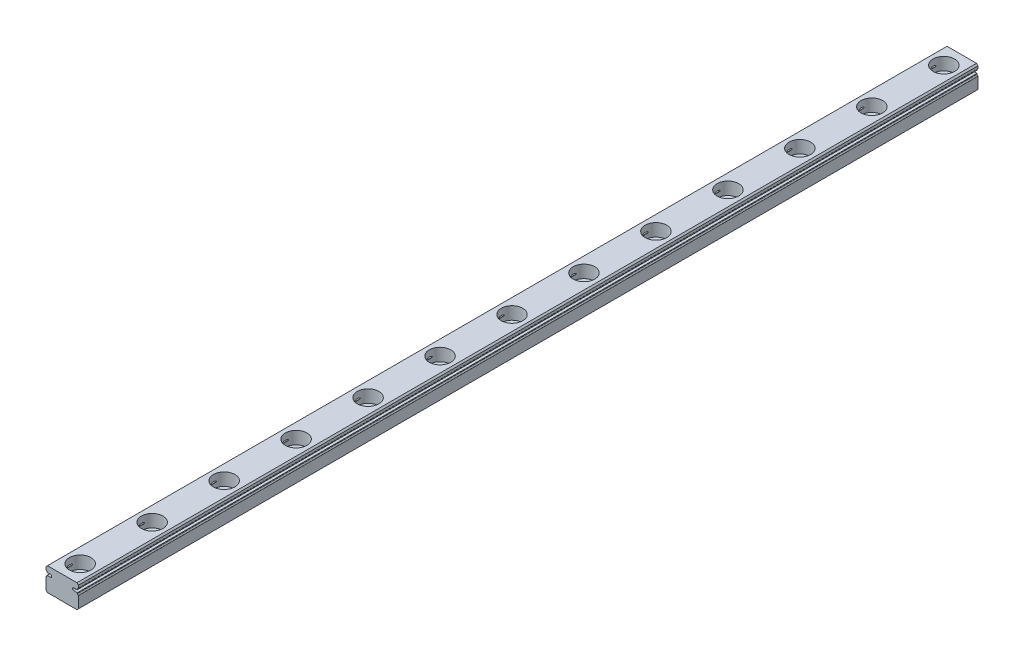
SolidWorks part; units mm, degrees
ref_plane "Alzado" through (0, 0, 0) normal (0, 0, 1) x (1, 0, 0)
ref_plane "Planta" through (0, 0, 0) normal (0, 1, 0) x (1, 0, 0)
ref_plane "Vista lateral" through (0, 0, 0) normal (1, 0, 0) x (0, 0, -1)
ref_plane "Plano1" through (0, 3.3057, 0) normal (0, 1, 0) x (1, 0, 0)
sketch "Croquis1" plane through (0, 3.3057, 0) normal (0, 1, 0) x (1, 0, 0)
  line L0 (4.5, 0) -> (-4.5, 0)
  line L1 (-4.5, 0) -> (-4.5, -250)
  line L2 (-4.5, -250) -> (4.5, -250)
  line L3 (4.5, -250) -> (4.5, 0)
  dimension "D1" = 9
  dimension "D2" = 250
extrude "Saliente-Extruir1" add sketch "Croquis1" against normal blind 6.5
sketch "Croquis2" plane through (0, 0, 0) normal (0, 0, -1) x (-1, 0, 0)
  line L0 (1.6, -3.1943) -> (2.1, -3.1943)
  arc A0 (2.1, -3.1943) -> (1.6, -3.1943) centre (1.85, -3.4568) ccw
extrude "Cortar-Extruir1" cut sketch "Croquis2" against normal through all
sketch "Croquis3" plane through (0, 0, 0) normal (0, 0, -1) x (-1, 0, 0)
  line L0 (-4.5, 1.6457) -> (-4.5, 0.9457)
  line L1 (-4.5, 0.9457) -> (-3.25, 0.9457)
  line L2 (-3.25, 1.6457) -> (-4.5, 1.6457)
  arc A0 (-3.25, 0.9457) -> (-3.25, 1.6457) centre (-3.25, 1.2957) ccw
extrude "Cortar-Extruir2" cut sketch "Croquis3" against normal through all
sketch "Croquis4" plane through (0, 0, 0) normal (0, 0, -1) x (-1, 0, 0)
  line L0 (-4.3353, 0.9457) -> (-4.5, 0.9457)
  line L1 (-4.5, 0.9457) -> (-4.5, 0.4169)
  arc A0 (-4.5, 0.4169) -> (-4.3353, 0.9457) centre (-4.622, 0.745) ccw
extrude "Cortar-Extruir3" cut sketch "Croquis4" against normal through all
sketch "Croquis5" plane through (0, 0, 0) normal (0, 0, -1) x (-1, 0, 0)
  line L0 (-4.5, 2.1744) -> (-4.5, 1.6457)
  line L1 (-4.5, 1.6457) -> (-4.3353, 1.6457)
  arc A0 (-4.3353, 1.6457) -> (-4.5, 2.1744) centre (-4.622, 1.8464) ccw
extrude "Cortar-Extruir4" cut sketch "Croquis5" against normal through all
sketch "Croquis6" plane through (0, 0, 0) normal (0, 0, -1) x (-1, 0, 0)
  line L0 (4.5, 0.9457) -> (4.5, 1.6457)
  line L1 (4.5, 1.6457) -> (3.25, 1.6457)
  line L2 (3.25, 0.9457) -> (4.5, 0.9457)
  arc A0 (3.25, 1.6457) -> (3.25, 0.9457) centre (3.25, 1.2957) ccw
extrude "Cortar-Extruir5" cut sketch "Croquis6" against normal through all
sketch "Croquis7" plane through (0, 0, 0) normal (0, 0, -1) x (-1, 0, 0)
  line L0 (4.3353, 1.6457) -> (4.5, 1.6457)
  line L1 (4.5, 1.6457) -> (4.5, 2.1744)
  arc A0 (4.5, 2.1744) -> (4.3353, 1.6457) centre (4.622, 1.8464) ccw
extrude "Cortar-Extruir6" cut sketch "Croquis7" against normal through all
sketch "Croquis8" plane through (0, 0, 0) normal (0, 0, -1) x (-1, 0, 0)
  line L0 (4.5, 0.4169) -> (4.5, 0.9457)
  line L1 (4.5, 0.9457) -> (4.3353, 0.9457)
  arc A0 (4.3353, 0.9457) -> (4.5, 0.4169) centre (4.622, 0.745) ccw
extrude "Cortar-Extruir7" cut sketch "Croquis8" against normal through all
hole_wizard "Refrentado para tornillo con cabeza hexagonal de M31" positions "Croquis10" profile "Croquis9" counterbore size "M3" standard "Ansi Metric"
sketch "Croquis10" plane through (0, 3.3057, 0) normal (0, 1, 0) x (1, 0, 0)
  line L0 (-4.5, -250) -> (4.5, -250) construction
  point P0 (0, -245)
  point P1 (0, -225)
  point P2 (0, -205)
  point P3 (0, -185)
  point P4 (0, -165)
  point P5 (0, -145)
  point P6 (0, -125)
  point P7 (0, -105)
  point P8 (0, -85)
  point P9 (0, -65)
  point P10 (0, -45)
  point P11 (0, -25)
  point P12 (0, -5)
  dimension "D1" = 5
  dimension "D2" = 20
  dimension "D3" = 20
  dimension "D4" = 20
  dimension "D5" = 20
  dimension "D6" = 20
  dimension "D7" = 20
  dimension "D8" = 20
  dimension "D9" = 20
  dimension "D10" = 20
  dimension "D11" = 20
  dimension "D12" = 20
  dimension "D13" = 20
sketch "Croquis9" plane through (0, 3.3057, 245) normal (1, 0, 0) x (0, 0, 1)
  line L0 (0, 0) -> (0, 6.5)
  line L1 (0, 6.5) -> (1.75, 6.5)
  line L3 (1.75, 6.5) -> (1.75, 3.5)
  line L4 (1.75, 3.5) -> (3, 3.5)
  line L5 (3, 3.5) -> (3, 0)
  line L7 (3, 0) -> (0, 0)
  line L11 (0, -6.35) -> (0, 107.95) construction
  dimension "Diámetro de taladro hasta el siguiente" = 3.5
  dimension "Profundidad de taladro hasta el siguiente" = 6.5
  dimension "Diámetro de refrentado" = 6
  dimension "Profundidad de refrentado" = 3.5
chamfer "Chaflán1" distance 0.4 angle 45 4 edges at (-4.5, -3.1943, 125) (-4.5, 3.3057, 125) (4.5, -3.1943, 125) (4.5, 3.3057, 125)
chamfer "Chaflán2" distance 0.011 angle 36.529 4 edges at (-4.5, 2.1744, 125) (4.5, 0.4169, 125) (-4.5, 0.4169, 125) (4.5, 2.1744, 125) first distance on face at (-4.3528, 1.9303, 125) first distance on face at (4.3528, 0.6611, 125) first distance on face at (-4.5, -1.1887, 125) first distance on face at (4.5, 2.5401, 125)
chamfer "Chaflán3" distance 0.151 angle 53.471 4 edges at (-4.3353, 0.9457, 125) (4.3353, 0.9457, 125) (-4.3353, 1.6457, 125) (4.3353, 1.6457, 125) first distance on face at (-3.7926, 0.9457, 125) first distance on face at (4.3493, 0.6648, 125) first distance on face at (-4.3493, 1.9266, 125) first distance on face at (3.7926, 1.6457, 125)
